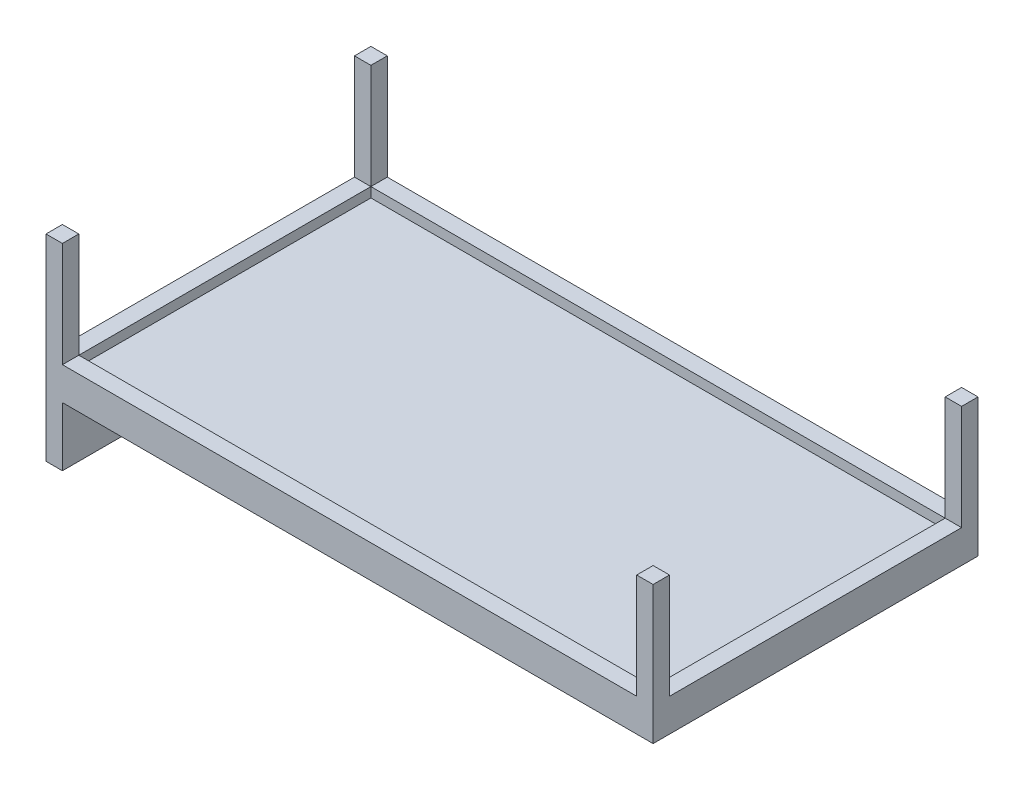
SolidWorks part; units mm, degrees
ref_plane "前视基准面" through (0, 0, 0) normal (0, 0, 1) x (1, 0, 0)
ref_plane "上视基准面" through (0, 0, 0) normal (0, 1, 0) x (1, 0, 0)
ref_plane "右视基准面" through (0, 0, 0) normal (1, 0, 0) x (0, 0, -1)
sketch "草图1" plane through (0, 0, 0) normal (0, 1, 0) x (1, 0, 0)
  line L1 (-82.8848, 54.9091) -> (102.1152, 54.9091)
  line L2 (-82.8848, 54.9091) -> (-82.8848, -44.0909)
  line L3 (-82.8848, -44.0909) -> (102.1152, -44.0909)
  line L4 (102.1152, 54.9091) -> (102.1152, -44.0909)
  point P4 (0, 0)
  dimension "D1" = 185
  dimension "D2" = 99
extrude "凸台-拉伸1" add sketch "草图1" along normal blind 5
sketch "草图3" plane through (0, 0, 0) normal (0, 1, 0) x (1, 0, 0)
  line L0 (-77.8848, 49.9091) -> (-77.8848, 54.9091)
  line L1 (-82.8848, 54.9091) -> (102.1152, 54.9091)
  line L2 (-82.8848, 54.9091) -> (-82.8848, -44.0909)
  line L3 (-82.8848, -44.0909) -> (102.1152, -44.0909)
  line L4 (102.1152, 54.9091) -> (102.1152, -44.0909)
  line L5 (-77.8848, 49.9091) -> (97.1152, 49.9091)
  line L6 (-77.8848, 49.9091) -> (-77.8848, -39.0909)
  line L7 (-77.8848, -39.0909) -> (97.1152, -39.0909)
  line L8 (97.1152, 49.9091) -> (97.1152, -39.0909)
  line L9 (-77.8848, -39.0909) -> (-82.8848, -39.0909)
  dimension "D1" = 185
  dimension "D2" = 99
  dimension "D3" = 175
  dimension "D4" = 89
  dimension "D5" = 5
  dimension "D6" = 5
extrude "凸台-拉伸2" add sketch "草图3" along normal blind 8 contours L9 L6 L0 L1 L2 | L7 L9 L2 L3 L4 L1 L0 L5 L8 region at (-80.3848, 0, -7.9091) region at (-75.7865, 0, -52.4091)
extrude "凸台-拉伸3" add sketch "草图3<3>" against normal blind 2 contours L7 L9 L2 L3 L4 L1 L0 L5 L8 | L9 L6 L0 L1 L2 region at (-80.3848, 0, -7.9091) region at (-75.7865, 0, -52.4091)
sketch "草图3<3>" plane through (0, 0, 0) normal (0, 1, 0) x (1, 0, 0) same geometry as "草图3"
sketch "草图4" plane through (0, 0, 0) normal (0, 1, 0) x (1, 0, 0)
  line L0 (-82.8848, -44.0909) -> (102.1152, -44.0909) construction
  line L1 (-82.8848, 54.9091) -> (-77.8848, 54.9091)
  line L2 (-82.8848, 54.9091) -> (-82.8848, -44.0909)
  line L3 (-82.8848, -44.0909) -> (-77.8848, -44.0909)
  line L4 (-77.8848, 54.9091) -> (-77.8848, -44.0909)
  dimension "D1" = 5
extrude "凸台-拉伸4" add sketch "草图4" against normal blind 20
sketch "草图5" plane through (0, 0, 0) normal (0, 1, 0) x (1, 0, 0)
  line L0 (97.1152, 49.9091) -> (-77.8848, 49.9091) construction
  line L1 (-82.8848, 54.9091) -> (-77.8848, 54.9091)
  line L2 (-82.8848, 54.9091) -> (-82.8848, 49.9091)
  line L3 (-82.8848, 49.9091) -> (-77.8848, 49.9091)
  line L4 (-77.8848, 54.9091) -> (-77.8848, 49.9091)
  line L5 (-77.8848, 49.9091) -> (97.1152, 49.9091) construction
  line L7 (97.1152, 49.9091) -> (102.1152, 49.9091)
  line L8 (97.1152, 49.9091) -> (97.1152, 54.9091)
  line L9 (97.1152, 54.9091) -> (102.1152, 54.9091)
  line L10 (102.1152, 49.9091) -> (102.1152, 54.9091)
  line L11 (102.1152, -44.0909) -> (97.1152, -44.0909)
  line L12 (102.1152, -44.0909) -> (102.1152, -39.0909)
  line L13 (102.1152, -39.0909) -> (97.1152, -39.0909)
  line L14 (97.1152, -44.0909) -> (97.1152, -39.0909)
  line L15 (-82.8848, -44.0909) -> (-77.8848, -44.0909)
  line L16 (-82.8848, -44.0909) -> (-82.8848, -39.0909)
  line L17 (-82.8848, -39.0909) -> (-77.8848, -39.0909)
  line L18 (-77.8848, -44.0909) -> (-77.8848, -39.0909)
extrude "凸台-拉伸5" add sketch "草图5" along normal blind 40
